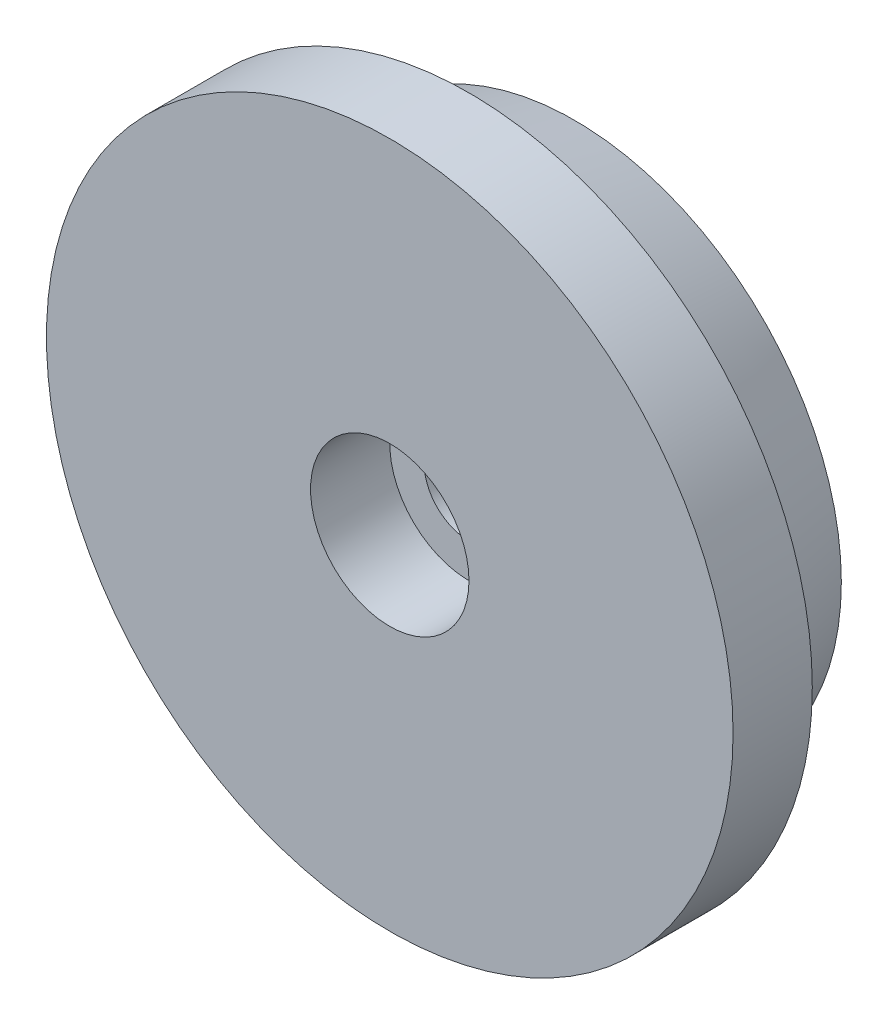
SolidWorks part; units mm, degrees
material "Custom Plastic"
ref_plane "Front Plane" through (0, 0, 0) normal (0, 0, 1) x (1, 0, 0)
ref_plane "Top Plane" through (0, 0, 0) normal (0, 1, 0) x (1, 0, 0)
ref_plane "Right Plane" through (0, 0, 0) normal (1, 0, 0) x (0, 0, -1)
sketch "Sketch1" plane through (0, 0, 0) normal (0, 0, 1) x (1, 0, 0)
  circle A3 centre (132.5, 0) radius 13 construction
  circle A4 centre (132.5, 0) radius 13
  circle A5 centre (132.5, 0) radius 3
extrude "Boss-Extrude1" add sketch "Sketch1" along normal blind 3
sketch "Sketch2" plane through (0, 0, 0) normal (0, 0, -1) x (-1, 0, 0)
  circle A2 centre (-132.5, 0) radius 1.7
  circle A3 centre (-132.5, 0) radius 11.1
extrude "Boss-Extrude2" add sketch "Sketch2" along normal blind 4
chamfer "Chamfer1" distance 4 distance2 1 1 edges at (121.4, 0, -4) first distance on face at (121.4, 0, -4)
